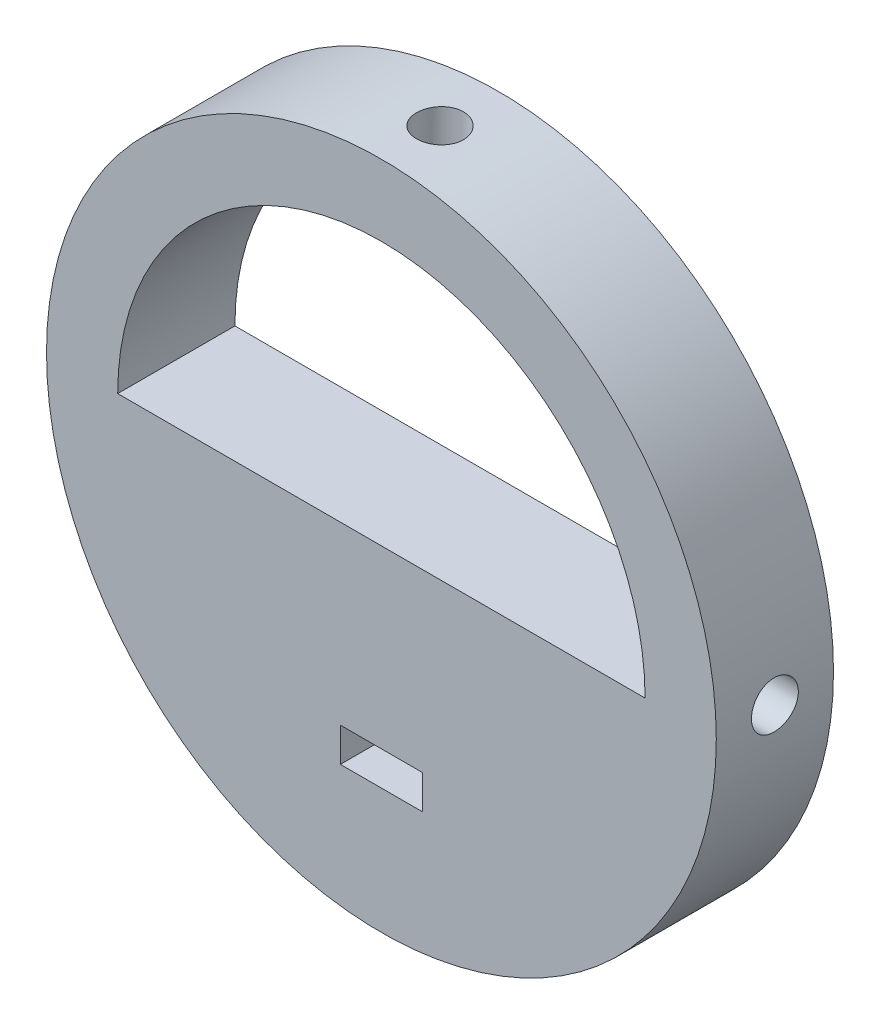
SolidWorks part; units mm, degrees
ref_plane "Front Plane" through (0, 0, 0) normal (0, 0, 1) x (1, 0, 0)
ref_plane "Top Plane" through (0, 0, 0) normal (0, 1, 0) x (1, 0, 0)
ref_plane "Right Plane" through (0, 0, 0) normal (1, 0, 0) x (0, 0, -1)
sketch "Sketch1" plane through (0, 0, 0) normal (0, 0, 1) x (1, 0, 0)
  circle A0 centre (0, 0) radius 28.575
  dimension "D1" = 57.15
extrude "Boss-Extrude1" add sketch "Sketch1" along normal blind 5 and the other way blind 5
sketch "Sketch15" plane through (0, 0, 0) normal (0, 1, 0) x (1, 0, 0)
  circle A0 centre (0, 0) radius 2
  dimension "D1" = 4
extrude "Cut-Extrude12" cut sketch "Sketch15" against normal blind 5 from offset 29
sketch "Sketch16" plane through (0, 0, 0) normal (1, 0, 0) x (0, 0, -1)
  circle A0 centre (0, 0) radius 2
  dimension "D1" = 4
extrude "Cut-Extrude13" cut sketch "Sketch16" along normal blind 5 from offset 29 offset against normal yes
sketch "Sketch19" plane through (0, 0, 0) normal (0, 1, 0) x (1, 0, 0)
  line L1 (0, 4.0415) -> (-3.5, 2.0207)
  line L2 (-3.5, 2.0207) -> (-3.5, -2.0207)
  line L3 (-3.5, -2.0207) -> (0, -4.0415)
  line L4 (0, -4.0415) -> (3.5, -2.0207)
  line L5 (3.5, -2.0207) -> (3.5, 2.0207)
  line L6 (3.5, 2.0207) -> (0, 4.0415)
  circle A0 centre (0, 0) radius 3.5 construction
  dimension "D1" = 7
extrude "Cut-Extrude14" cut sketch "Sketch19" against normal blind 2.9 from offset 15 offset against normal yes
sketch "Sketch20" plane through (0, 0, 0) normal (0, 0, 1) x (1, 0, 0)
  line L0 (-22.5, 0) -> (22.5, 0)
  arc A0 (22.5, 0) -> (-22.5, 0) centre (0, 0) ccw
  point P4 (0, 0)
  dimension "D1" = 45
extrude "Cut-Extrude15" cut sketch "Sketch20" against normal through all and the other way through all
mirror "Mirror1" about plane through (0, 0, 0) normal (1, 0, 0) of "Cut-Extrude13"
sketch "Sketch21" plane through (0, 0, 5) normal (0, 0, 1) x (1, 0, 0)
  line L1 (-3.5, -15) -> (3.5, -15)
  line L2 (-3.5, -15) -> (-3.5, -17.9)
  line L3 (-3.5, -17.9) -> (3.5, -17.9)
  line L4 (3.5, -15) -> (3.5, -17.9)
  line L5 (-3.5, -15) -> (3.5, -17.9) construction
  line L6 (-3.5, -17.9) -> (3.5, -15) construction
  point P0 (0, -16.45)
  point P5 (0, -15)
  dimension "D1" = 7
  dimension "D2" = 15
  dimension "D3" = 0
  dimension "D4" = 2.9
extrude "Cut-Extrude16" cut sketch "Sketch21" against normal blind 5
sketch "Sketch22" plane through (0, -17.9, 0) normal (0, 1, 0) x (1, 0, 0)
  circle A0 centre (0, 0) radius 2
  dimension "D1" = 4
extrude "Cut-Extrude17" cut sketch "Sketch22" against normal through all
